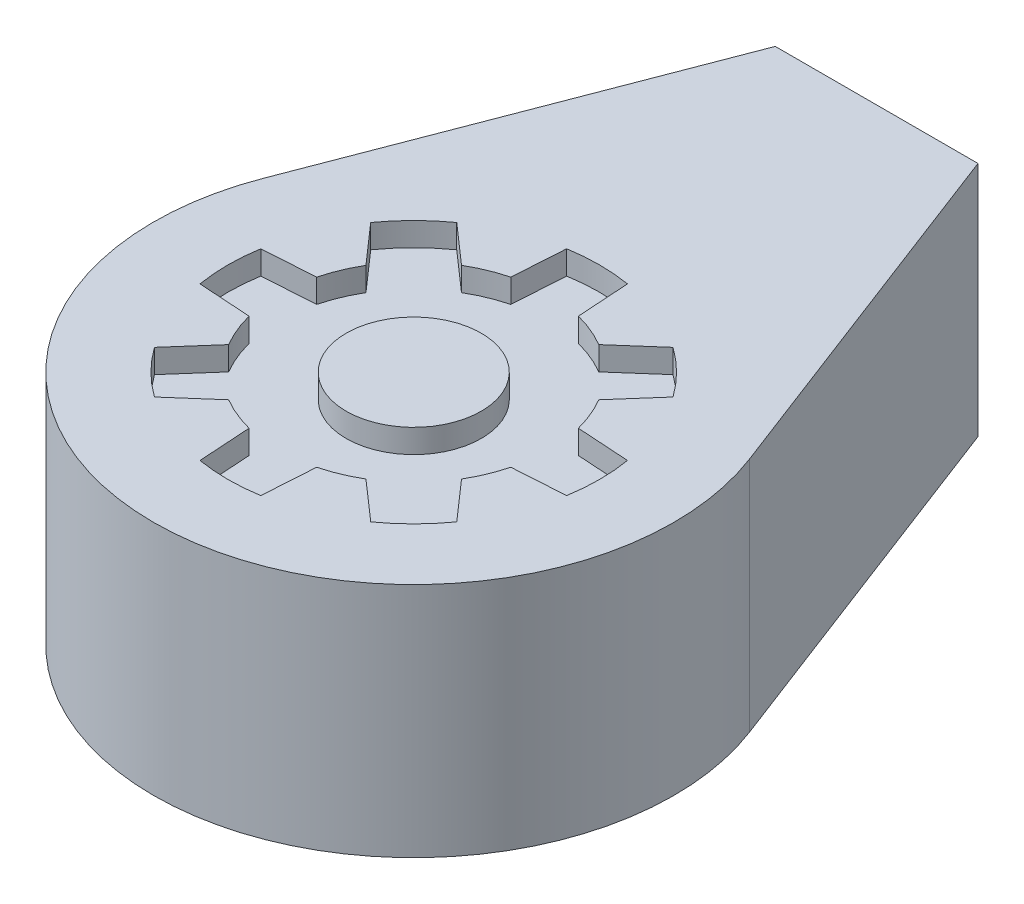
SolidWorks part; units mm, degrees
ref_plane "Front Plane" through (0, 0, 0) normal (0, 0, 1) x (1, 0, 0)
ref_plane "Top Plane" through (0, 0, 0) normal (0, 1, 0) x (1, 0, 0)
ref_plane "Right Plane" through (0, 0, 0) normal (1, 0, 0) x (0, 0, -1)
sketch "Sketch1" plane through (0, 0, 0) normal (0, 1, 0) x (1, 0, 0)
  line L1 (-2.5, -8.8013) -> (2.5, -8.8013)
  line L2 (-2.5, -8.8013) -> (-2.5, 8.8013)
  line L3 (-2.5, 8.8013) -> (2.5, 8.8013)
  line L4 (2.5, -8.8013) -> (2.5, 8.8013)
  line L5 (-2.5, -8.8013) -> (2.5, 8.8013) construction
  line L6 (-2.5, 8.8013) -> (2.5, -8.8013) construction
  circle A0 centre (0, 0) radius 6.7
  circle A1 centre (0, 0) radius 7.7
  dimension "D1" = 13.4
  dimension "D3" = 5
  dimension "D2" = 1
extrude "Boss-Extrude1" add sketch "Sketch1" along normal blind 6 contours L2 A1 A0 | L2 A1 L4 A0 | L4 A1 A0 region at (-7.5453, 0, 0) region at (0, 0, 7.0492) region at (2.6547, 0, 6.7495)
sketch "Sketch2" plane through (0, 6, 0) normal (0, 1, 0) x (1, 0, 0)
  line L0 (0, 0) -> (0, 15.5073) construction
  line L1 (-3, 13.7) -> (3, 13.7)
  line L2 (3, 13.7) -> (7.191, 2.7531)
  line L3 (-3, 13.7) -> (-7.191, 2.7531)
  line L4 (-7.191, 2.7531) -> (7.191, 2.7531) construction
  circle A0 centre (0, 0) radius 7.7
  point P8 (0, 13.7)
  line M5 (-2.5, 6.2161) -> (-2.5, 7.2829)
  arc M6 (-2.5, 7.2829) -> (2.5, 7.2829) centre (0, 0) ccw
  line M7 (2.5, 7.2829) -> (2.5, 6.2161)
  arc M8 (2.5, 6.2161) -> (-2.5, 6.2161) centre (0, 0) cw
  dimension "D1" = 6
  dimension "D2" = 6
extrude "Boss-Extrude2" add sketch "Sketch2" along normal blind 1 contours A0 L2 L1 L3 M6 | M8 M5 M6 M7 | A0 M7 M5 M8 region at (0, 6, -9.7849) region at (-5.1995, 6, -5.3845) region at (0, 6, -0.2464)
sketch "Sketch3" plane through (0, 6, 0) normal (0, -1, 0) x (1, 0, 0)
  line L0 (-3, -13.7) -> (-7.191, -2.7531)
  line L1 (-7.191, -2.7531) -> (-6.2571, -2.3955)
  line L2 (-4.9003, -5.9394) -> (-1.9292, -13.7) construction
  line L3 (-3, -13.7) -> (3, -13.7) construction
  line L4 (-1.9292, -13.7) -> (-3, -13.7)
  line L5 (-3, -13.7) -> (-7.191, -2.7531) construction
  line L6 (-2.5, -7.2829) -> (-1.9292, -13.7)
  line L7 (-2.5, -6.2161) -> (-2.5, -7.2829) construction
  line L8 (-6.2571, -2.3955) -> (-4.9003, -5.9394) construction
  line L9 (0, 0) -> (0, -17.6457) construction
  line L10 (1.9292, -13.7) -> (3, -13.7)
  line L11 (3, -13.7) -> (7.191, -2.7531)
  line L12 (2.5, -7.2829) -> (1.9292, -13.7)
  arc A0 (7.191, -2.7531) -> (2.5, -7.2829) centre (0, 0) cw
  arc A1 (2.5, -7.2829) -> (-2.5, -7.2829) centre (0, 0) ccw construction
  arc A2 (-7.191, -2.7531) -> (-2.5, -7.2829) centre (0, 0) ccw
  arc M8 (-2.5, -7.2829) -> (-7.191, -2.7531) centre (0, 0) cw
  line M9 (-7.191, -2.7531) -> (-3, -13.7)
  line M10 (-3, -13.7) -> (3, -13.7)
  line M11 (3, -13.7) -> (7.191, -2.7531)
  arc M12 (7.191, -2.7531) -> (2.5, -7.2829) centre (0, 0) cw
  dimension "D1" = 1
extrude "Boss-Extrude3" add sketch "Sketch3" along normal blind 6 contours L6 M8 M9 M10 | L12 M12 M10 M11 region at (3.7057, 6, -9.1939) region at (-3.7057, 6, -9.1939)
sketch "Sketch4" plane through (0, 7, 0) normal (0, 1, 0) x (1, 0, 0)
  line L0 (0, 0) -> (0, 5.5) construction
  line L1 (-0.9, 5.4259) -> (-1, 3.873)
  line L2 (0.9, 5.4259) -> (1, 3.873)
  line L3 (-1, 3.873) -> (1, 3.873) construction
  line L4 (0.9, 5.4259) -> (-0.9, 5.4259) construction
  line L5 (3.2003, 4.4731) -> (2.0315, 3.4457)
  line L6 (4.4731, 3.2003) -> (3.4457, 2.0315)
  line L7 (5.4259, 0.9) -> (3.873, 1)
  line L8 (5.4259, -0.9) -> (3.873, -1)
  line L9 (4.4731, -3.2003) -> (3.4457, -2.0315)
  line L10 (3.2003, -4.4731) -> (2.0315, -3.4457)
  line L11 (0.9, -5.4259) -> (1, -3.873)
  line L12 (-0.9, -5.4259) -> (-1, -3.873)
  line L13 (-3.2003, -4.4731) -> (-2.0315, -3.4457)
  line L14 (-4.4731, -3.2003) -> (-3.4457, -2.0315)
  line L15 (-5.4259, -0.9) -> (-3.873, -1)
  line L16 (-5.4259, 0.9) -> (-3.873, 1)
  line L17 (-4.4731, 3.2003) -> (-3.4457, 2.0315)
  line L18 (-3.2003, 4.4731) -> (-2.0315, 3.4457)
  circle A0 centre (0, 0) radius 4
  circle A1 centre (0, 0) radius 5.5
  point P40 (0, 0)
  dimension "D1" = 8
  dimension "D2" = 11
  dimension "D3" = 2
  dimension "D4" = 1.8
  dimension "D5" = 8
extrude "Cut-Extrude1" cut sketch "Sketch4" against normal blind 0.7 contours A0 | L18 A1 L17 A0 | L16 A1 L15 A0 | L14 A1 L13 A0 | L12 A1 L11 A0 | L10 A1 L9 A0 | L8 A1 L7 A0 | L6 A1 L5 A0 | L2 A1 L1 A0 region at (0, 7, -4.7034) region at (0, 7, 0) region at (-3.3258, 7, -3.3258) region at (3.3258, 7, -3.3258) region at (-4.7034, 7, 0) region at (4.7034, 7, 0) region at (-3.3258, 7, 3.3258) region at (3.3258, 7, 3.3258) region at (0, 7, 4.7034)
sketch "Sketch5" plane through (0, 6.3, 0) normal (0, 1, 0) x (1, 0, 0)
  circle A0 centre (0, 0) radius 2
  dimension "D1" = 4
extrude "Boss-Extrude4" add sketch "Sketch5" along normal up to surface (0.7 mm away) up to face at (0, 7, 0)
